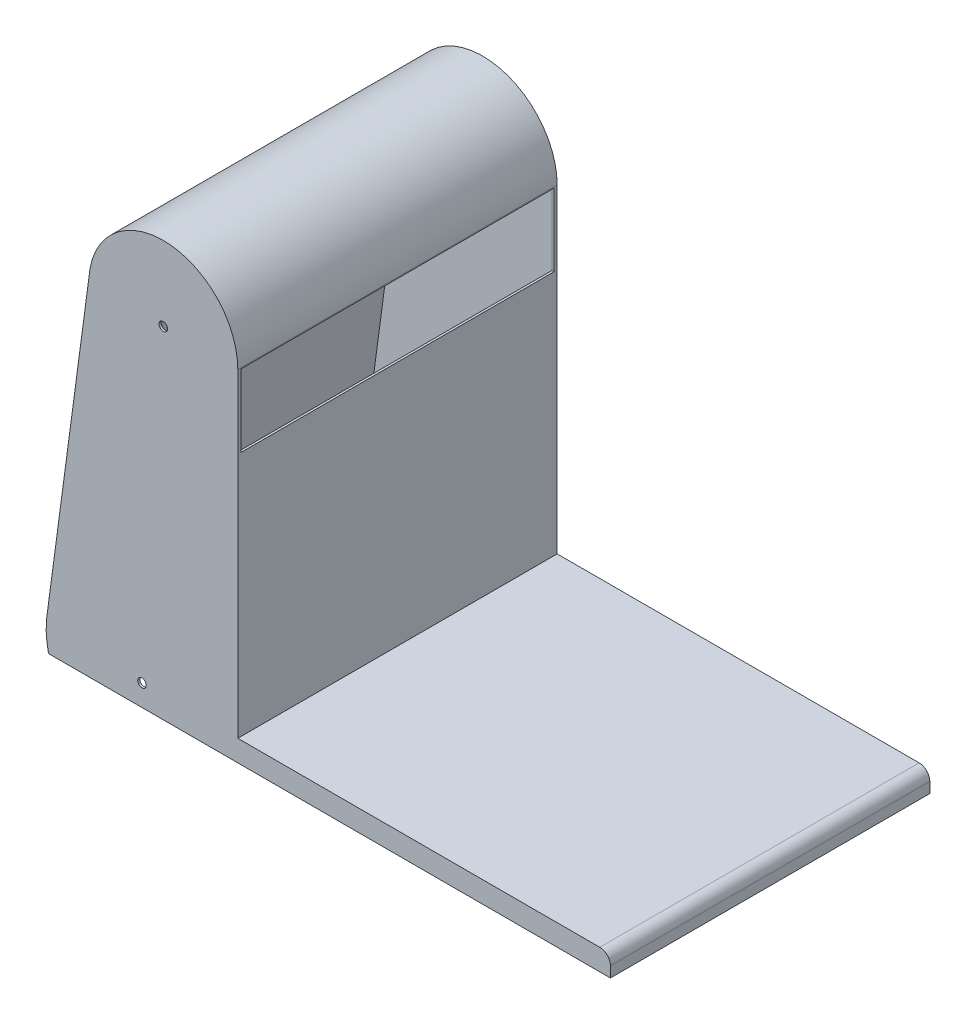
SolidWorks part; units mm, degrees
ref_plane "前视基准面" through (0, 0, 0) normal (0, 0, 1) x (1, 0, 0)
ref_plane "上视基准面" through (0, 0, 0) normal (0, 1, 0) x (1, 0, 0)
ref_plane "右视基准面" through (0, 0, 0) normal (1, 0, 0) x (0, 0, -1)
sketch "草图1" plane through (0, 0, 0) normal (0, 0, 1) x (1, 0, 0)
  line L0 (440, -20) -> (440, 0)
  line L1 (0, -20) -> (400, -20)
  line L2 (400, -20) -> (440, -20)
  line L3 (0, -20) -> (-87.7496, -20)
  line L4 (440, 0) -> (90, 0)
  line L5 (90, 0) -> (90, 300)
  line L10 (-49.845, 304.6563) -> (-89.8007, 5.9867)
  arc A0 (-89.8007, 5.9867) -> (-87.7496, -20) centre (0, 0) ccw
  arc A1 (90, 300) -> (-49.845, 304.6563) centre (20, 300) ccw
extrude "凸台-拉伸1" add sketch "草图1" against normal blind 300
fillet "圆角1" radius 10 1 edges at (440, 0, -150)
shell "抽壳1" thickness 2 removed face at (176.1252, -20, -150)
sketch "草图2" plane through (0, 0, 0) normal (0, 0, 1) x (1, 0, 0)
  circle A0 centre (0, 0) radius 4
  circle A1 centre (20, 300) radius 4
extrude "切除-拉伸1" cut sketch "草图2" against normal through all
sketch "草图3" plane through (0, 0, 0) normal (0, 0, 1) x (1, 0, 0)
  line L0 (88.0227, 0) -> (90, 0)
  line L1 (87.7496, -20) -> (85.7205, -20)
  arc A0 (87.7496, -20) -> (90, 0) centre (0, 0) ccw
  arc A1 (85.7205, -20) -> (88.0227, 0) centre (0, 0) ccw
extrude "凸台-拉伸2" add sketch "草图3" against normal up to surface (300 mm away) up to face at (4, 0, -300)
sketch "草图4" plane through (88, 0, 0) normal (-1, 0, 0) x (0, 0, 1)
  line L5 (-7, 231) -> (-3, 231)
  line L6 (-293, 299) -> (-7, 299)
  line L8 (-293, 299) -> (-297, 299)
  line L9 (-297, 299) -> (-297, 231)
  line L13 (-297, 231) -> (-7, 231)
  line L14 (-3, 231) -> (-3, 299)
  line L15 (-3, 299) -> (-7, 299)
extrude "切除-拉伸12" cut sketch "草图4" against normal blind 10
